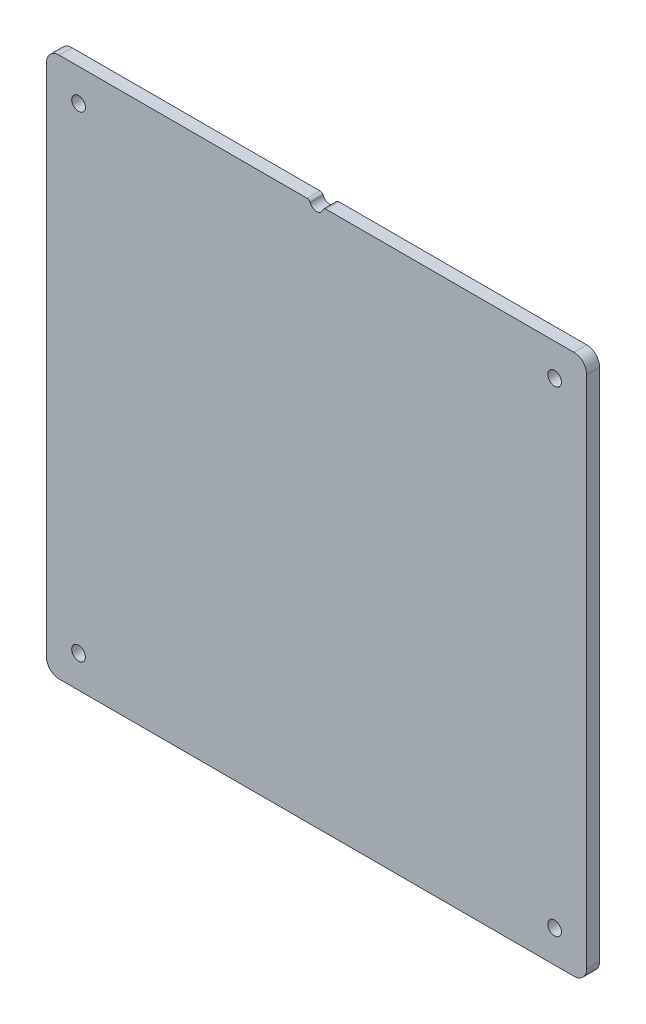
SolidWorks part; units mm, degrees
material "PC High Viscosity"
ref_plane "Front Plane" through (0, 0, 0) normal (0, 0, 1) x (1, 0, 0)
ref_plane "Top Plane" through (0, 0, 0) normal (0, 1, 0) x (1, 0, 0)
ref_plane "Right Plane" through (0, 0, 0) normal (1, 0, 0) x (0, 0, -1)
sketch "Sketch1" plane through (0, 0, 0) normal (0, 0, 1) x (1, 0, 0)
  line L1 (-133.35, -133.35) -> (133.35, -133.35)
  line L2 (-133.35, -133.35) -> (-133.35, 133.35)
  line L3 (-133.35, 133.35) -> (133.35, 133.35)
  line L4 (133.35, -133.35) -> (133.35, 133.35)
  line L5 (-133.35, -133.35) -> (133.35, 133.35) construction
  line L6 (-133.35, 133.35) -> (133.35, -133.35) construction
  point P0 (0, 0)
  dimension "D1" = 266.7
extrude "Boss-Extrude1" add sketch "Sketch1" along normal blind 6.35
hole_wizard "1/4 Clearance Hole1" positions "Sketch2" profile "Sketch3" hole size "1/4" standard "ANSI Inch" end condition through all
sketch "Sketch2" plane through (0, 0, 6.35) normal (0, 0, 1) x (1, 0, 0)
  line L0 (0, 133.35) -> (0, -133.35) construction
  line L1 (133.35, 133.35) -> (-133.35, 133.35) construction
  line L2 (-133.35, -133.35) -> (133.35, -133.35) construction
  line L3 (-133.35, 0) -> (133.35, 0) construction
  line L4 (-133.35, 133.35) -> (-133.35, -133.35) construction
  line L5 (133.35, -133.35) -> (133.35, 133.35) construction
  line L7 (-103.1875, -103.1875) -> (103.1875, -103.1875) construction
  line L8 (-103.1875, -103.1875) -> (-103.1875, 103.1875) construction
  line L9 (-103.1875, 103.1875) -> (103.1875, 103.1875) construction
  line L10 (103.1875, -103.1875) -> (103.1875, 103.1875) construction
  line L11 (-103.1875, -103.1875) -> (103.1875, 103.1875) construction
  line L12 (-103.1875, 103.1875) -> (103.1875, -103.1875) construction
  line L13 (-133.35, 104.775) -> (-117.475, 104.775) construction
  line L16 (-104.775, 117.475) -> (-104.775, 133.35) construction
  arc A0 (-117.475, 104.775) -> (-104.775, 117.475) centre (-117.475, 117.475) ccw construction
  point P0 (-117.475, 117.475)
  point P17 (-117.475, -117.475)
  point P19 (117.475, -117.475)
  point P20 (117.475, 117.475)
  point P143 (0, 0)
  point P144 (95.2096, -117.475)
  point P145 (0, 0)
  dimension "D4" = 12.7
  dimension "D1" = 15.875
  dimension "D2" = 15.875
  dimension "D3" = 206.375
sketch "Sketch3" plane through (-117.475, 117.475, 6.35) normal (1, 0, 0) x (0, -1, 0)
  line L0 (0, 0) -> (0, 6.35)
  line L1 (0, 6.35) -> (3.3782, 6.35)
  line L2 (3.3782, 6.35) -> (3.3782, 0)
  line L5 (3.3782, 0) -> (0, 0)
  line L11 (0, -6.35) -> (0, 107.95) construction
  dimension "Thru Hole Dia." = 6.7564
  dimension "Thru Hole Depth" = 6.35
fillet "Fillet1" radius 6.35 4 edges at (133.35, -133.35, 3.175) (-133.35, -133.35, 3.175) (133.35, 133.35, 3.175) (-133.35, 133.35, 3.175)
sketch "Sketch4" plane through (0, 0, 6.35) normal (0, 0, 1) x (1, 0, 0)
  line L0 (127, 133.35) -> (-127, 133.35) construction
  circle A0 centre (0, 133.35) radius 3.302
  dimension "D1" = 6.604
extrude "Cut-Extrude1" cut sketch "Sketch4" against normal through all
fillet "Fillet2" radius 1.5875 2 edges at (3.302, 133.35, 3.175) (-3.302, 133.35, 3.175)
